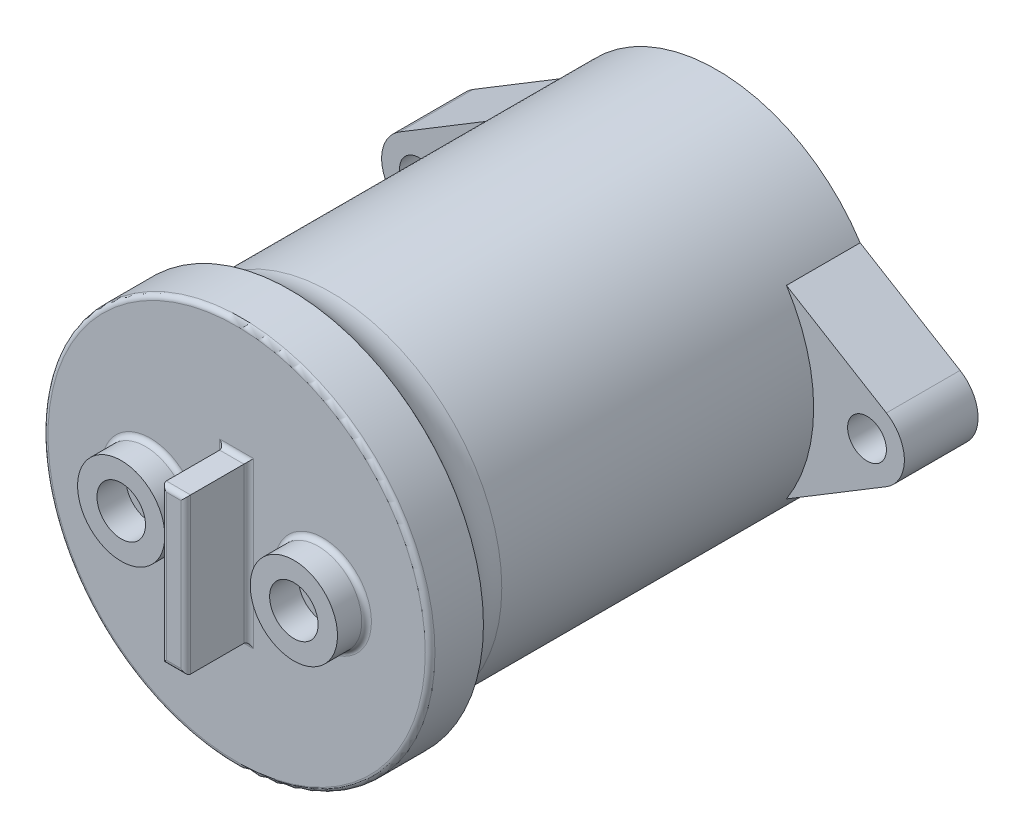
SolidWorks part; units mm, degrees
material "Custom Plastic"
ref_plane "X-Y Datum" through (0, 0, 0) normal (0, 0, 1) x (1, 0, 0)
ref_plane "X-Z Datum" through (0, 0, 0) normal (0, 1, 0) x (1, 0, 0)
ref_plane "Y-Z Datum" through (0, 0, 0) normal (1, 0, 0) x (0, 0, -1)
sketch "Sketch2" plane through (0, 0, 0) normal (0, 0, 1) x (1, 0, 0)
  circle A0 centre (0, 0) radius 17.6
  dimension "D1" = 35.2
extrude "Boss-Extrude1" add sketch "Sketch2" along normal blind 52.5
sketch "Sketch3" plane through (0, 0, 0) normal (0, 0, 1) x (1, 0, 0)
  line L0 (-23.1, 0) -> (23.1, 0) construction
  line L1 (-26.95, 0) -> (26.95, 0) construction
  line L2 (-25.095, 3.2928) -> (-14.794, 9.534)
  line L3 (-25.095, -3.2928) -> (-14.794, -9.534)
  line L4 (0, 28.5555) -> (0, -28.5555) construction
  line L5 (25.095, -3.2928) -> (14.794, -9.534)
  line L6 (25.095, 3.2928) -> (14.794, 9.534)
  circle A0 centre (23.1, 0) radius 2
  circle A1 centre (-23.1, 0) radius 2
  circle A2 centre (23.1, 0) radius 3.85
  circle A3 centre (-23.1, 0) radius 3.85
  circle A6 centre (0, 0) radius 17.6 construction
  circle A8 centre (0, 0) radius 17.6
  circle A9 centre (0, 0) radius 17.6
  point P4 (0, 0)
  point P10 (0, 0)
  point P23 (0, 0)
  dimension "D2" = 4
  dimension "D1" = 46.2
  dimension "D3" = 53.9
  dimension "D4" = 0
extrude "Boss-Extrude2" add sketch "Sketch3" along normal blind 7.6 contours A9 A2 L6 | A9 L5 A2 | A9 A2 A0 | A9 A3 A1 | A9 A3 L3 | A9 L2 A3 region at (-18.9017, 0, 0) region at (-21.2638, 3.2595, 0) region at (18.9017, 0, 0) region at (26.3595, 1.8362, 0)
sketch "Sketch4" plane through (0, 0, 52.5) normal (0, 0, 1) x (1, 0, 0)
  line L0 (-8.9, 0) -> (8.9, 0) construction
  line L1 (-1.25, 8) -> (1.25, 8)
  line L2 (-1.25, 8) -> (-1.25, -8)
  line L3 (-1.25, -8) -> (1.25, -8)
  line L4 (1.25, 8) -> (1.25, -8)
  line L5 (-1.25, 8) -> (1.25, -8) construction
  line L6 (-1.25, -8) -> (1.25, 8) construction
  circle A0 centre (-8.9, 0) radius 2.5
  circle A1 centre (8.9, 0) radius 2.5
  circle A2 centre (-8.9, 0) radius 4.5
  circle A3 centre (8.9, 0) radius 4.5
  point P0 (0, 0)
  point P11 (0, 0)
  dimension "D4" = 5
  dimension "D5" = 9
  dimension "D1" = 2.5
  dimension "D2" = 16
  dimension "D3" = 17.8
extrude "Boss-Extrude3" add sketch "Sketch4" along normal blind 3.5 contours L2 L1 L4 L3
sketch "Sketch5" plane through (0, 0, 52.5) normal (0, 0, 1) x (1, 0, 0)
  line L4 (1.25, 8) -> (-1.25, 8)
  line L5 (1.25, -8) -> (1.25, 8)
  line L6 (-1.25, -8) -> (1.25, -8)
  line L7 (-1.25, 8) -> (-1.25, -8)
  line L8 (1.25, 8) -> (-1.25, 8)
  line L9 (1.25, -8) -> (1.25, 8)
  line L10 (-1.25, -8) -> (1.25, -8)
  line L11 (-1.25, 8) -> (-1.25, -8)
  circle A1 centre (8.9, 0) radius 4.5
  circle A2 centre (8.9, 0) radius 4.5
  circle A3 centre (-8.9, 0) radius 4.5
  circle A4 centre (-8.9, 0) radius 4.5
  circle A5 centre (8.9, 0) radius 2.5
  circle A6 centre (8.9, 0) radius 2.5
  circle A7 centre (-8.9, 0) radius 2.5
  circle A8 centre (-8.9, 0) radius 2.5
  circle M22 centre (0, 0) radius 17.6
  line M23 (1.25, 8) -> (1.25, -8)
  line M24 (1.25, -8) -> (-1.25, -8)
  line M25 (-1.25, -8) -> (-1.25, 8)
  line M26 (-1.25, 8) -> (1.25, 8)
  dimension "D1" = 0
  dimension "D2" = 0
  dimension "D3" = 0
  dimension "D4" = 0
  dimension "D5" = 0
extrude "Cut-Extrude1" cut sketch "Sketch5" against normal blind 3 contours A4 A2 M22 M26 M23 M24 M25 | A8 | A6 region at (8.9, 0, 52.5) region at (-8.9, 0, 52.5) region at (-17.1022, 0, 52.5)
sketch "Sketch7" plane through (0, 0, 49.5) normal (0, 0, 1) x (1, 0, 0)
  circle A0 centre (0, 0) radius 19.95
  dimension "D1" = 39.9
extrude "Boss-Extrude5" add sketch "Sketch7" against normal blind 5.5
fillet "Fillet3" radius 5 1 edges at (17.6, 0, 44)
fillet "Fillet4" radius 0.5 11 edges at (-1.25, 0, 56) (0, 8, 56) (1.25, 0, 56) (0, -8, 56) (19.95, 0, 49.5) (-1.25, 0, 49.5) (0, -8, 49.5) (1.25, 0, 49.5) (0, 8, 49.5) (13.4, 0, 49.5) (-4.4, 0, 49.5)
